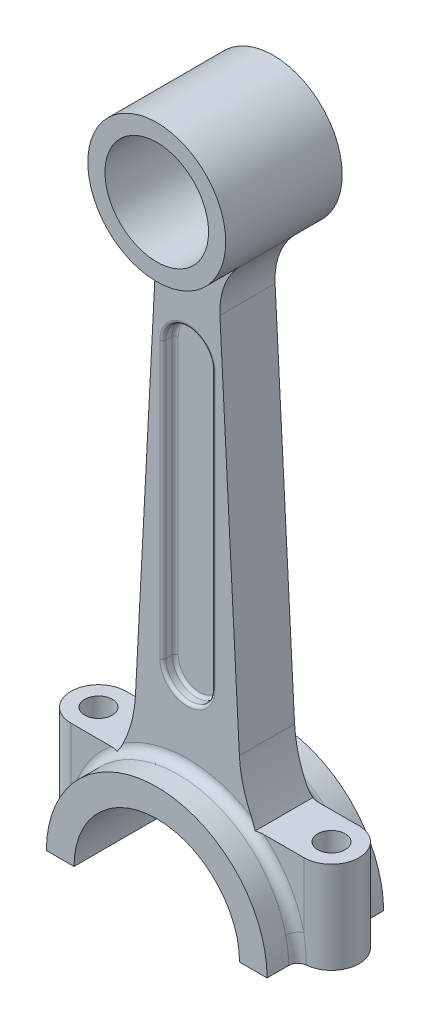
SolidWorks part; units mm, degrees
material "AISI 4340 Steel, annealed"
ref_plane "Front Plane" through (0, 0, 0) normal (0, 0, 1) x (1, 0, 0)
ref_plane "Top Plane" through (0, 0, 0) normal (0, 1, 0) x (1, 0, 0)
ref_plane "Right Plane" through (0, 0, 0) normal (1, 0, 0) x (0, 0, -1)
sketch "Sketch1" plane through (0, 0, 0) normal (0, 0, 1) x (1, 0, 0)
  line L0 (0, 0) -> (0, -201.2) construction
  line L1 (-10, -20.1556) -> (-17.8497, -169.9368)
  line L2 (10, -20.1556) -> (17.8497, -169.9368)
  line L3 (-36, -201.2) -> (-27, -201.2)
  line L4 (27, -201.2) -> (36, -201.2)
  circle A0 centre (0, 0) radius 22.5
  circle A1 centre (0, 0) radius 16.9
  arc A2 (27, -201.2) -> (-27, -201.2) centre (0, -201.2) ccw
  arc A3 (36, -201.2) -> (-36, -201.2) centre (0, -201.2) ccw
  dimension "D1" = 45
  dimension "D2" = 33.8
  dimension "D3" = 54
  dimension "D4" = 72
  dimension "D5" = 201.2
  dimension "D6" = 20
  dimension "D7" = 6
extrude "Boss-Extrude1" add sketch "Sketch1" along normal mid plane 38 contours A1 A0 | A3 A2 | L3 A2 L4 A3 region at (-11.5231, 18.5805, 0) region at (0, -166.005, 0)
extrude "Boss-Extrude2" add sketch "Sketch1<3>" along normal mid plane 18 contours L0 A0 L1 A3 | A0 L0 A3 L2 region at (7.1843, -100.8455, 0) region at (-7.1843, -100.8455, 0)
sketch "Sketch1<3>" plane through (0, 0, 0) normal (0, 0, 1) x (1, 0, 0) same geometry as "Sketch1"
sketch "Sketch3" plane through (0, 0, 9) normal (0, 0, 1) x (1, 0, 0)
  line L0 (0, 0) -> (0, -186.9184) construction
  line L1 (0, -138.4592) -> (0, -48.4592) construction
  line L2 (-8, -138.4592) -> (-8, -48.4592)
  line L3 (8, -138.4592) -> (8, -48.4592)
  arc A0 (-8, -138.4592) -> (8, -138.4592) centre (0, -138.4592) ccw
  arc A1 (8, -48.4592) -> (-8, -48.4592) centre (0, -48.4592) ccw
  point P5 (0, -93.4592)
  dimension "D2" = 8
  dimension "D1" = 90
extrude "Cut-Extrude1" cut sketch "Sketch3" against normal blind 4
mirror "Mirror1" about plane through (0, 0, 0) normal (0, 0, 1) of "Cut-Extrude1"
fillet "Fillet1" radius 1 16 edges at (0, -40.4592, -9) (8, -93.4592, -9) (0, -146.4592, -9) (0, -40.4592, 9) (8, -93.4592, 9) (0, -146.4592, 9) (0, -40.4592, 5) (8, -93.4592, 5) (0, -146.4592, 5) (8, -93.4592, -5) (0, -40.4592, -5) (-8, -93.4592, -5) (0, -146.4592, -5) (-8, -93.4592, -9) (-8, -93.4592, 9) (-8, -93.4592, 5)
ref_plane "Plane1" through (0, -171.2, 0) normal (0, -1, 0) x (-1, 0, 0)
fillet "Fillet2" radius 40 2 edges at (17.8497, -169.9368, 0) (-17.8497, -169.9368, 0)
fillet "Fillet4" radius 22.5 2 edges at (10, -20.1556, 0) (-10, -20.1556, 0)
sketch "Sketch4" plane through (0, -171.2, 0) normal (0, -1, 0) x (-1, 0, 0)
  line L0 (38, 0) -> (-38, 0) construction
  line L1 (38, -9) -> (-38, -9)
  line L2 (38, 9) -> (-38, 9)
  arc A0 (38, -9) -> (38, 9) centre (38, 0) ccw
  arc A1 (-38, 9) -> (-38, -9) centre (-38, 0) ccw
  point P2 (0, 0)
  dimension "D2" = 9
  dimension "D1" = 76
extrude "Boss-Extrude3" add sketch "Sketch4" along normal up to surface (30 mm away) up to face at (-31.5, -201.2, 0)
sketch "Sketch5" plane through (0, 0, 9) normal (0, 0, 1) x (1, 0, 0)
  line L1 (-27, -201.2) -> (27, -201.2)
  line L2 (-27, -201.2) -> (27, -201.2)
  arc A1 (27, -201.2) -> (-27, -201.2) centre (0, -201.2) ccw
  arc A2 (27, -201.2) -> (-27, -201.2) centre (0, -201.2) ccw
  dimension "D1" = 0
extrude "Cut-Extrude2" cut sketch "Sketch5" against normal through all
sketch "Sketch6" plane through (0, -171.2, 0) normal (0, 1, 0) x (1, 0, 0)
  circle A0 centre (38, 0) radius 4.5
  circle A1 centre (-38, 0) radius 4.5
  dimension "D1" = 9
  dimension "D2" = 9
extrude "Cut-Extrude3" cut sketch "Sketch6" against normal through all
fillet "Fillet6" radius 3 2 edges at (0, -165.2, 9) (0, -165.2, -9)
